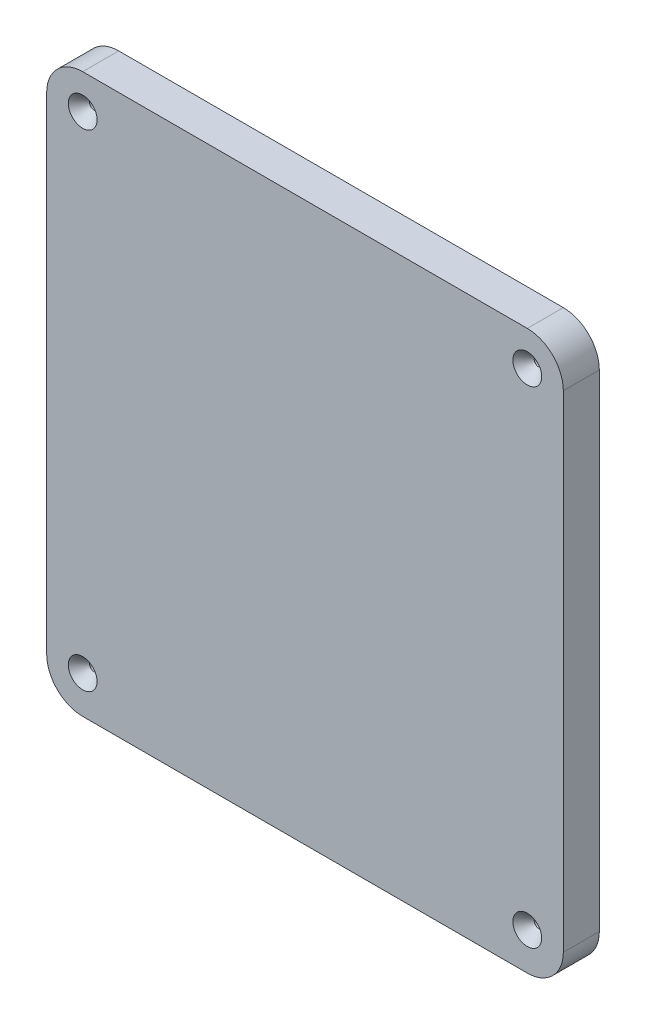
SolidWorks part; units mm, degrees
material "Beech"
ref_plane "Front Plane" through (0, 0, 0) normal (0, 0, 1) x (1, 0, 0)
ref_plane "Top Plane" through (0, 0, 0) normal (0, 1, 0) x (1, 0, 0)
ref_plane "Right Plane" through (0, 0, 0) normal (1, 0, 0) x (0, 0, -1)
sketch "Sketch1" plane through (0, 0, 0) normal (0, 0, 1) x (1, 0, 0)
  line L0 (139.05, 899.8522) -> (139.05, 151.949) construction
  line L1 (-43.1, 899.8522) -> (-43.1, 151.949) construction
  line L2 (-43.1, 906.2022) -> (139.05, 906.2022) construction
  line L8 (139.05, 668.0772) -> (139.05, 864.9272)
  line L9 (139.05, 864.9272) -> (-43.1, 864.9272)
  line L10 (-43.1, 864.9272) -> (-43.1, 668.0772)
  line L11 (-43.1, 668.0772) -> (139.05, 668.0772)
  dimension "D1" = 196.85
  dimension "D2" = 41.275
extrude "Boss-Extrude1" add sketch "Sketch1" along normal blind 12.7
fillet "Fillet1" radius 12.7 4 edges at (139.05, 864.9272, 6.35) (139.05, 668.0772, 6.35) (-43.1, 668.0772, 6.35) (-43.1, 864.9272, 6.35)
hole_wizard "Hole1" positions "Sketch2" profile "Sketch3" legacy
sketch "Sketch2" plane through (47.975, -440.3076, 12.7) normal (0, 0, 1) x (1, 0, 0)
  point P0 (-78.375, 1293.0392)
  point P3 (-78.375, 1121.5892)
  point P6 (78.375, 1121.5892)
  point P9 (78.375, 1293.0392)
  point P12 (-764.0155, 1530.0782)
sketch "Sketch3" plane through (-30.4, 852.7316, 12.7) normal (1, 0, 0) x (0, -1, 0)
  line L0 (0, 0) -> (0, 32.7039)
  line L1 (0, 32.7039) -> (1.5875, 31.75)
  line L2 (1.5875, 31.75) -> (1.5875, 4.0177)
  line L3 (1.5875, 4.0177) -> (5.08, 0)
  line L4 (5.08, 0) -> (0, 0)
  line L5 (0, -14.3089) -> (0, 102.4216) construction
  line L6 (0, 32.7039) -> (-1.5875, 31.75) construction
  line L7 (-1.5875, 4.0177) -> (-5.08, 0) construction
  dimension "Diameter" = 3.175
  dimension "Depth" = 31.75
  dimension "C-Sink Diameter" = 10.16
  dimension "C-Sink Angle" = 82
  dimension "Drill Angle" = 118
